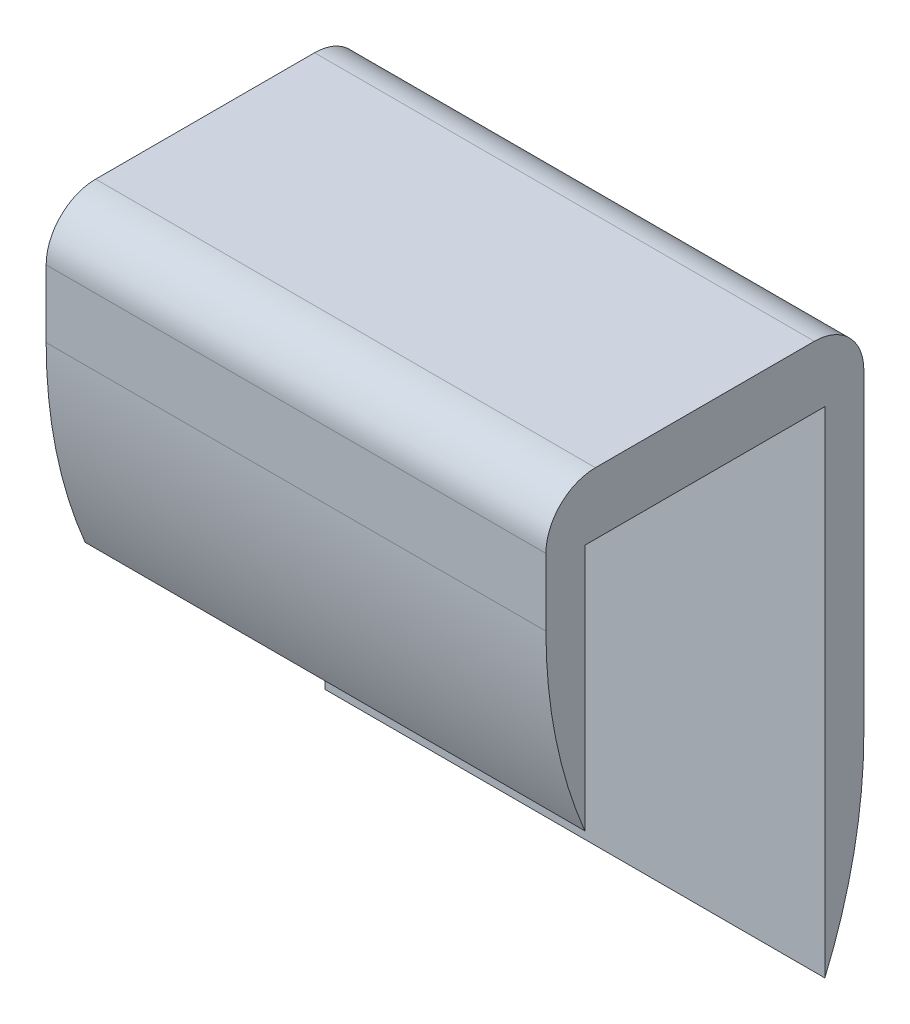
SolidWorks part; units mm, degrees
ref_plane "Front Plane" through (0, 0, 0) normal (0, 0, 1) x (1, 0, 0)
ref_plane "Top Plane" through (0, 0, 0) normal (0, 1, 0) x (1, 0, 0)
ref_plane "Right Plane" through (0, 0, 0) normal (1, 0, 0) x (0, 0, -1)
sketch "Sketch1" plane through (0, 0, 0) normal (1, 0, 0) x (0, 0, -1)
  line L0 (-8.1595, -12.7) -> (-6.1595, -12.7)
  line L1 (-6.1595, -12.7) -> (-6.1595, 0)
  line L2 (-6.1595, 0) -> (6.1595, 0)
  line L3 (6.1595, 0) -> (6.1595, -25.4)
  line L4 (6.1595, -25.4) -> (8.1595, -25.4)
  line L5 (8.1595, -25.4) -> (8.1595, 3.175)
  line L6 (8.1595, 3.175) -> (-8.1595, 3.175)
  line L7 (-8.1595, 3.175) -> (-8.1595, -12.7)
  point P6 (0, 0)
  dimension "D1" = 2
  dimension "D2" = 12.7
  dimension "D3" = 3.175
  dimension "D4" = 12.319
  dimension "D5" = 25.4
extrude "Boss-Extrude1" add sketch "Sketch1" along normal blind 25.654
fillet "Fillet1" radius 25.4 2 edges at (12.827, -12.7, 8.1595) (12.827, -25.4, -8.1595)
fillet "Fillet2" radius 2.54 2 edges at (12.827, 3.175, -8.1595) (12.827, 3.175, 8.1595)
equation "\"Height\"= 12in"
equation "\"Depth\"= 7in"
equation "\"WallThickness\"= 0.25in"
equation "\"FloorThickness\"= 0.25in"
equation "\"Width\" = 30in"
equation "\"D4@Sketch1\"=\"WallThickness\"*2-.015"
